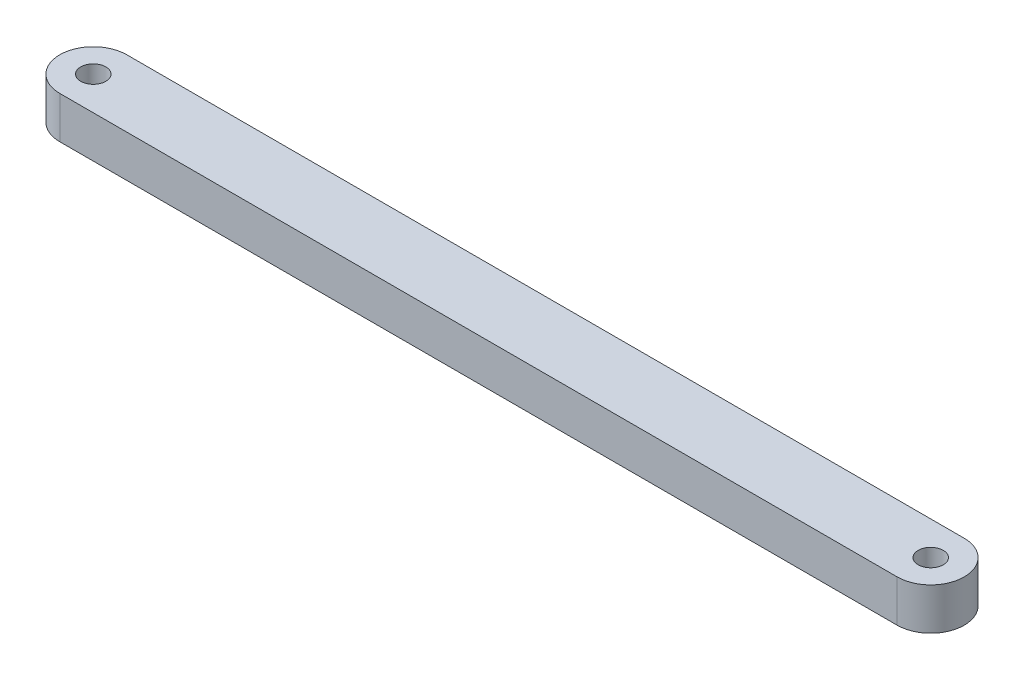
SolidWorks part; units mm, degrees
ref_plane "Front Plane" through (0, 0, 0) normal (0, 0, 1) x (1, 0, 0)
ref_plane "Top Plane" through (0, 0, 0) normal (0, 1, 0) x (1, 0, 0)
ref_plane "Right Plane" through (0, 0, 0) normal (1, 0, 0) x (0, 0, -1)
sketch "Sketch1" plane through (0, 0, 0) normal (0, 1, 0) x (1, 0, 0)
  line L0 (-50, 0) -> (50, 0) construction
  line L1 (-50, 4) -> (50, 4)
  line L2 (-50, -4) -> (50, -4)
  arc A0 (-50, 4) -> (-50, -4) centre (-50, 0) ccw
  arc A1 (50, -4) -> (50, 4) centre (50, 0) ccw
  circle A2 centre (-50, 0) radius 1.5
  circle A3 centre (50, 0) radius 1.5
  point P3 (0, 0)
  dimension "D2" = 4
  dimension "D3" = 3
  dimension "D1" = 100
extrude "Boss-Extrude1" add sketch "Sketch1" along normal blind 5 contours L2 A1 L1 A0 | A3 | A2
